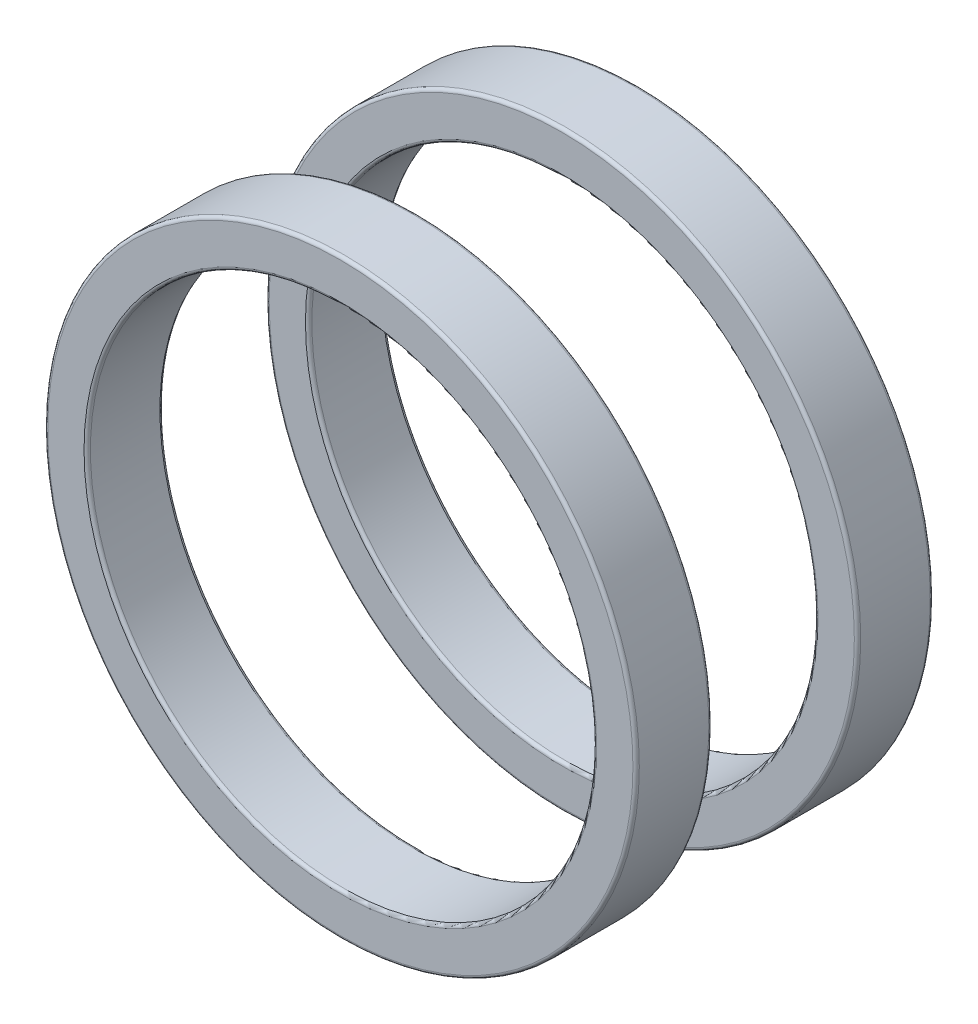
SolidWorks part; units mm, degrees
material "Stainless Steel (ferritic)"
ref_plane "Front Plane" through (0, 0, 0) normal (0, 0, 1) x (1, 0, 0)
ref_plane "Top Plane" through (0, 0, 0) normal (0, 1, 0) x (1, 0, 0)
ref_plane "Right Plane" through (0, 0, 0) normal (1, 0, 0) x (0, 0, -1)
ref_axis "Central Axis" through (0, 0, -2.7381) along (0, 0, 1)
sketch "Outer Race Layout Sketch" plane through (0, 0, 0) normal (1, 0, 0) x (0, 0, -1)
  line L0 (-2.4892, 0) -> (2.4892, 0) construction
  line L1 (0, 6.35) -> (0, -6.35) construction
  line L2 (2.2403, 6.35) -> (-2.2403, 6.35)
  line L3 (-2.2403, 6.35) -> (-2.4892, 6.1011)
  line L4 (-2.4892, 6.1011) -> (-2.4892, 4.705)
  line L5 (-2.4892, 4.705) -> (-1.1063, 4.705)
  line L6 (2.4892, 4.705) -> (1.1063, 4.705)
  line L7 (2.4892, 6.1011) -> (2.4892, 4.705)
  line L8 (2.2403, 6.35) -> (2.4892, 6.1011)
  line L9 (0, 6.35) -> (0, 4.3656) construction
  line L10 (0, 4.3656) -> (0, 2.3813) construction
  arc A0 (-1.1063, 4.705) -> (1.1063, 4.705) centre (0, 4.3656) cw
  point P14 (0, 2.3813)
  dimension "Width" = 4.9784
  dimension "OD" = 12.7
  dimension "D1" = 45
  dimension "D2" = 0.2489
  dimension "Shaft Dia" = 4.7625
  dimension "D3" = 2.2126
  dimension "D4" = 0.3394
sketch "Inner Race Layout Sketch" plane through (0, 0, 0) normal (1, 0, 0) x (0, 0, -1)
  line L0 (-2.4892, 4.0262) -> (-1.1063, 4.0262)
  line L1 (0, 6.35) -> (0, -6.35) construction
  line L2 (-2.4892, 6.1011) -> (-2.4892, 4.705) construction
  line L3 (-2.4892, 4.0262) -> (-2.4892, 2.6302)
  line L4 (-2.2403, 6.35) -> (-2.4892, 6.1011) construction
  line L5 (-2.4892, 2.6302) -> (-2.2403, 2.3812)
  line L6 (-2.2403, 2.3812) -> (2.2403, 2.3813)
  line L8 (2.2403, 2.3813) -> (2.4892, 2.6302)
  line L10 (2.4892, 2.6302) -> (2.4892, 4.0262)
  line L11 (2.4892, 4.0262) -> (1.1063, 4.0262)
  line L12 (2.4892, 6.1011) -> (2.4892, 4.705) construction
  line L13 (2.2403, 6.35) -> (2.4892, 6.1011) construction
  arc A0 (1.1063, 4.705) -> (-1.1063, 4.705) centre (0, 4.3656) ccw construction
  arc A1 (1.1063, 4.0262) -> (-1.1063, 4.0262) centre (0, 4.3656) cw
sketch "Ball Layout Sketch" plane through (0, 0, 0) normal (1, 0, 0) x (0, 0, -1)
  line L0 (-1.1572, 4.3656) -> (1.1572, 4.3656)
  arc A2 (-1.1572, 4.3656) -> (1.1572, 4.3656) centre (0, 4.3656) cw
  arc A3 (1.1063, 4.705) -> (-1.1063, 4.705) centre (0, 4.3656) ccw construction
sketch "Bearing Shields Revolve Profile" plane through (0, 0, 0) normal (1, 0, 0) x (0, 0, -1)
  line L0 (-2.4892, 4.705) -> (-1.1063, 4.705) construction
  line L1 (-2.3139, 4.705) -> (-1.208, 4.705)
  line L2 (-2.3647, 4.6542) -> (-2.3647, 4.077)
  line L3 (-2.3139, 4.0262) -> (-1.208, 4.0262)
  line L4 (-1.1572, 4.6542) -> (-1.1572, 4.077)
  line L5 (-2.4892, 4.0262) -> (-1.1063, 4.0262) construction
  line L6 (2.4892, 4.705) -> (1.1063, 4.705) construction
  line L7 (2.3139, 4.705) -> (1.208, 4.705)
  line L8 (2.3647, 4.6542) -> (2.3647, 4.077)
  line L9 (2.3139, 4.0262) -> (1.208, 4.0262)
  line L10 (1.1572, 4.6542) -> (1.1572, 4.077)
  line L11 (2.4892, 4.0262) -> (1.1063, 4.0262) construction
  line L12 (-2.2403, 6.35) -> (-2.4892, 6.1011) construction
  arc A0 (2.3139, 4.705) -> (2.3647, 4.6542) centre (2.3139, 4.6542) cw
  arc A1 (2.3647, 4.077) -> (2.3139, 4.0262) centre (2.3139, 4.077) cw
  arc A2 (1.1572, 4.077) -> (1.208, 4.0262) centre (1.208, 4.077) ccw
  arc A3 (1.1572, 4.6542) -> (1.208, 4.705) centre (1.208, 4.6542) cw
  arc A4 (-1.208, 4.705) -> (-1.1572, 4.6542) centre (-1.208, 4.6542) cw
  arc A5 (-1.1572, 4.077) -> (-1.208, 4.0262) centre (-1.208, 4.077) cw
  arc A6 (-2.3647, 4.077) -> (-2.3139, 4.0262) centre (-2.3139, 4.077) ccw
  arc A7 (-2.3647, 4.6542) -> (-2.3139, 4.705) centre (-2.3139, 4.6542) cw
  point P18 (-2.3647, 6.2255)
  point P23 (2.3647, 4.705)
  point P28 (1.1572, 4.0262)
  point P35 (-1.1572, 4.0262)
  point P40 (-2.3647, 4.705)
  dimension "D1" = 0.0508
revolve "Bearing Shields Revolve" add sketch "Bearing Shields Revolve Profile" angle 360 about L0
equation "\"D2@Outer Race Layout Sketch\" = \"Width@Outer Race Layout Sketch\" * .05"
equation "\"D3@Outer Race Layout Sketch\" = \"Width@Outer Race Layout Sketch\" / 2.25"
equation "\"D4@Outer Race Layout Sketch\" =  (  (  ( \"OD@Outer Race Layout Sketch\" - \"Width@Outer Race Layout Sketch\" )  / 2 )  / 3.25 )  / 3.5"
